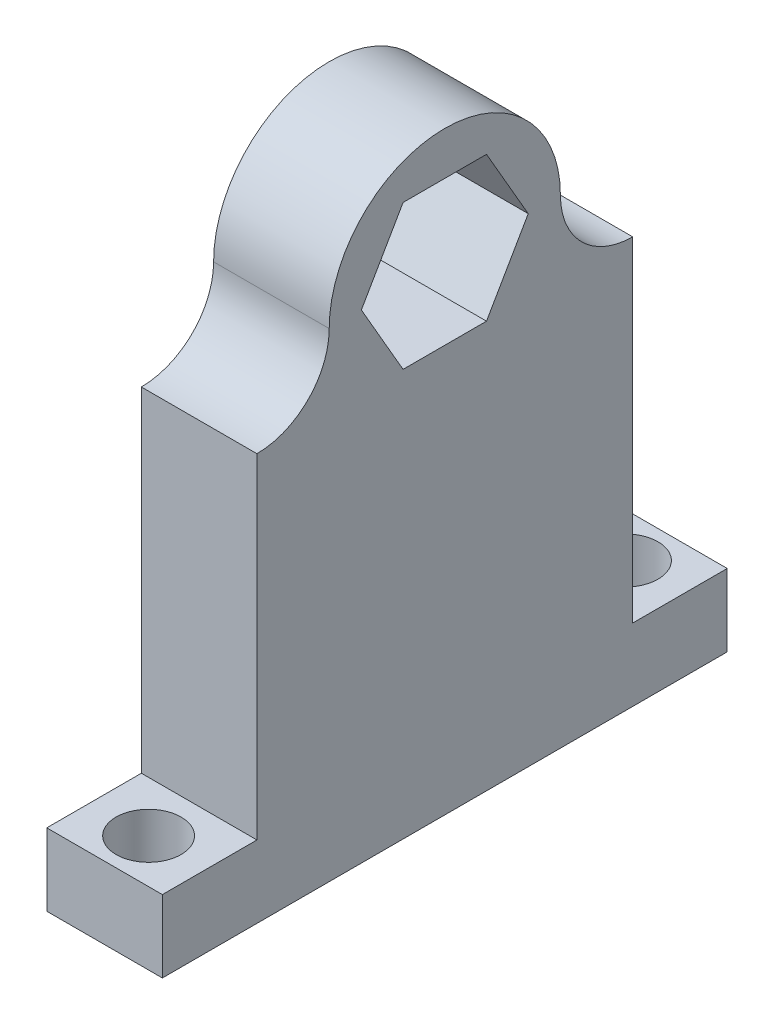
SolidWorks part; units mm, degrees
ref_plane "Спереди" through (0, 0, 0) normal (0, 0, 1) x (1, 0, 0)
ref_plane "Сверху" through (0, 0, 0) normal (0, 1, 0) x (1, 0, 0)
ref_plane "Справа" through (0, 0, 0) normal (1, 0, 0) x (0, 0, -1)
sketch "Эскиз1" plane through (0, 0, 0) normal (1, 0, 0) x (0, 0, -1)
  line L6 (-8, 0) -> (8, 0) construction
  line L12 (-13, -5) -> (-13, -10)
  line L13 (13, -5) -> (13, -10)
  line L15 (-13, -10) -> (13, -10)
  arc A0 (8, 0) -> (-8, 0) centre (0, 0) ccw
  arc A1 (-13, -5) -> (-8, 0) centre (-13, 0) ccw
  arc A2 (8, 0) -> (13, -5) centre (13, 0) ccw
  point P4 (0, 0)
  point P7 (0, -39.795)
  point P9 (0, 8)
  dimension "D1" = 16
  dimension "D4" = 10
  dimension "D5" = 10
  dimension "D2" = 5
extrude "Бобышка-Вытянуть1" add sketch "Эскиз1" along normal blind 8
sketch "Эскиз2" plane through (8, 0, 0) normal (1, 0, 0) x (0, 0, -1)
  line L1 (5.7735, 0) -> (2.8868, 5)
  line L2 (2.8868, 5) -> (-2.8868, 5)
  line L3 (-2.8868, 5) -> (-5.7735, 0)
  line L4 (-5.7735, 0) -> (-2.8868, -5)
  line L5 (-2.8868, -5) -> (2.8868, -5)
  line L6 (2.8868, -5) -> (5.7735, 0)
  circle A0 centre (0, 0) radius 5 construction
  dimension "D1" = 10
extrude "Вырез-Вытянуть1" cut sketch "Эскиз2" against normal through all
sketch "Эскиз4" plane through (0, -10, 0) normal (0, -1, 0) x (1, 0, 0)
  line L8 (0, 13) -> (0, -13)
  line L9 (0, -13) -> (8, -13)
  line L10 (8, -13) -> (8, 13)
  line L11 (8, 13) -> (0, 13)
  line L12 (0, 13) -> (0, -13)
  line L13 (0, -13) -> (8, -13)
  line L14 (8, -13) -> (8, 13)
  line L15 (8, 13) -> (0, 13)
  dimension "D1" = 0
extrude "Бобышка-Вытянуть2" add sketch "Эскиз4" along normal up to surface (23.15 mm away)
sketch "Эскиз5" plane through (0, -33.15, 0) normal (0, -1, 0) x (1, 0, 0)
  line L1 (0, 19.5455) -> (8, 19.5455)
  line L2 (0, 19.5455) -> (0, -19.5455)
  line L3 (0, -19.5455) -> (8, -19.5455)
  line L4 (8, 19.5455) -> (8, -19.5455)
  line L8 (4, -16.5) -> (4, 16.5) construction
  line L9 (8, -19.5455) -> (0, 19.5455) construction
  line L10 (0, -19.5455) -> (8, 19.5455) construction
  circle A0 centre (4, -16.5) radius 2.25
  circle A1 centre (4, 16.5) radius 2.25
  dimension "Диаметр001" = 4.5
  dimension "Диаметр002" = 4.5
  dimension "X001" = 4
  dimension "X002" = 4
  dimension "Y001" = 19.5455
  dimension "Y002" = 3.0455
  dimension "Y003" = 33
  dimension "Y004" = 3.0455
extrude "Бобышка-Вытянуть3" add sketch "Эскиз5" against normal blind 5
ref_axis "Ось_крепления_гайки_33" through (4, -33.15, -16.5) along (0, 1, 0)
ref_axis "Ось_крепления_гайки_34" through (4, -33.15, 16.5) along (0, 1, 0)
